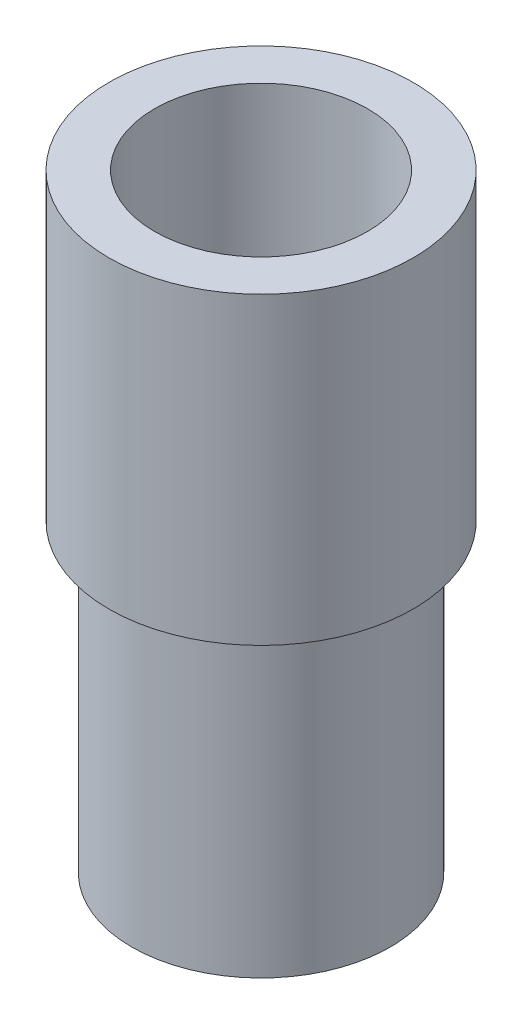
SolidWorks part; units mm, degrees
ref_plane "Front Plane" through (0, 0, 0) normal (0, 0, 1) x (1, 0, 0)
ref_plane "Top Plane" through (0, 0, 0) normal (0, 1, 0) x (1, 0, 0)
ref_plane "Right Plane" through (0, 0, 0) normal (1, 0, 0) x (0, 0, -1)
sketch "Sketch1" plane through (0, 0, 0) normal (0, 1, 0) x (1, 0, 0)
  circle A0 centre (0, 0) radius 6.375
  dimension "D1" = 12.75
extrude "Boss-Extrude1" add sketch "Sketch1" along normal blind 15
sketch "Sketch9" plane through (0, 15, 0) normal (0, 1, 0) x (1, 0, 0)
  circle A0 centre (0, 0) radius 7.5
  dimension "D1" = 15
extrude "Boss-Extrude5" add sketch "Sketch9" along normal blind 15
sketch "Sketch10" plane through (0, 30, 0) normal (0, 1, 0) x (1, 0, 0)
  circle A0 centre (0, 0) radius 5.25
  circle A1 centre (0, 0) radius 7.5 construction
  dimension "D1" = 2.25
extrude "Cut-Extrude4" cut sketch "Sketch10" against normal blind 10
sketch "Sketch11" plane through (0, 20, 0) normal (0, 1, 0) x (1, 0, 0)
  circle A0 centre (0, 0) radius 5.25
  circle A1 centre (0, 0) radius 5.25 construction
extrude "Cut-Extrude5" cut sketch "Sketch11" against normal blind 10 draft 20
sketch "Sketch12" plane through (0, 0, 0) normal (0, -1, 0) x (1, 0, 0)
  circle A0 centre (0, 0) radius 4.125
  circle A1 centre (0, 0) radius 6.375 construction
  dimension "D1" = 2.25
extrude "Cut-Extrude6" cut sketch "Sketch12" against normal up to surface (30 mm away) up to face at (0, 30, 5.25)
